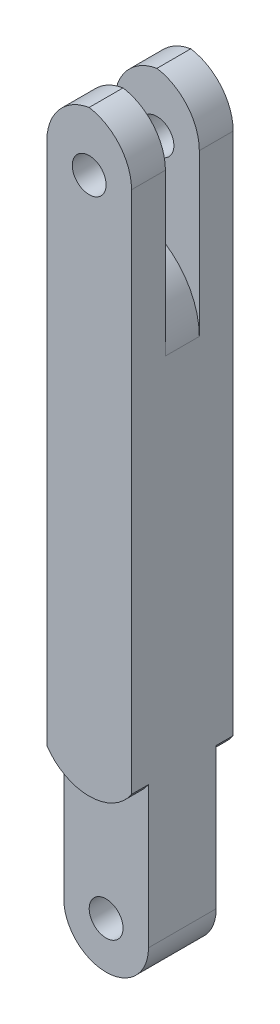
SolidWorks part; units mm, degrees
ref_plane "Alzado" through (0, 0, 0) normal (0, 0, 1) x (1, 0, 0)
ref_plane "Planta" through (0, 0, 0) normal (0, 1, 0) x (1, 0, 0)
ref_plane "Vista lateral" through (0, 0, 0) normal (1, 0, 0) x (0, 0, -1)
sketch "Croquis1" plane through (0, 0, 0) normal (0, 0, 1) x (1, 0, 0)
  line L0 (0, 0) -> (0, 42) construction
  line L1 (-2.5, -0.25) -> (-0.9682, -0.25)
  line L2 (-2.5, -0.25) -> (-2.5, 42)
  line L3 (-2.5, 42) -> (2.5, 42)
  line L4 (2.5, -0.25) -> (2.5, 42)
  line L5 (-4.5017, -1) -> (4.5216, -1) construction
  line L6 (0.9682, -0.25) -> (2.5, -0.25)
  circle A0 centre (0, 0) radius 1 construction
  circle A1 centre (0, 38.5) radius 1
  arc A2 (-0.9682, -0.25) -> (0.9682, -0.25) centre (0, 0) cw
  arc A3 (-2.5, -0.25) -> (2.5, -0.25) centre (0, -0.25) ccw
  circle A4 centre (0, 0) radius 1
  dimension "D1" = 2
  dimension "D3" = 2
  dimension "D7" = 2.5
  dimension "D2" = 0.75
  dimension "D4" = 38.5
  dimension "D5" = 3.5
  dimension "D6" = 5
extrude "Saliente-Extruir1" add sketch "Croquis1" along normal blind 6 contours A4 L1 A3 L6 | L1 A2 L6 L4 L3 L2 A1 region at (0, 20.8126, 0) region at (0, -1.4032, 0)
sketch "Croquis2" plane through (0, 42, 0) normal (0, 1, 0) x (1, 0, 0)
  line L0 (-2.5, -3) -> (2.5, -3) construction
  line L1 (-2.5, -6) -> (-2.5, 0) construction
  line L2 (2.5, -6) -> (2.5, 0) construction
  line L4 (-2.5, -2) -> (2.5, -2)
  line L5 (-2.5, -2) -> (-2.5, -4)
  line L6 (-2.5, -4) -> (2.5, -4)
  line L7 (2.5, -2) -> (2.5, -4)
  dimension "D1" = 2
extrude "Cortar-Extruir1" cut sketch "Croquis2" against normal blind 8
fillet "Redondeo1" radius 4.5 2 edges at (-2.5, 34, 3) (2.5, 34, 3)
fillet "Redondeo2" radius 3 4 edges at (-2.5, 42, 5) (-2.5, 42, 1) (2.5, 42, 1) (2.5, 42, 5)
sketch "Croquis3" plane through (0, 0, 6) normal (0, 0, 1) x (1, 0, 0)
  line L0 (0, 38.5) -> (0, 0) construction
  line L1 (0, 8) -> (0, 25.4165) construction
  line L2 (-3, 8) -> (-3, 25.4165)
  line L3 (3, 8) -> (3, 25.4165)
  line L4 (0, 38.5) -> (0, 25.4165) construction
  line L5 (3, 38.5) -> (3, 25.4165)
  line L6 (-3, 38.5) -> (-3, 25.4165)
  arc A0 (-3, 8) -> (3, 8) centre (0, 8) ccw
  arc A1 (3, 25.4165) -> (-3, 25.4165) centre (0, 25.4165) ccw
  arc A3 (3, 38.5) -> (-3, 38.5) centre (0, 38.5) ccw
  arc A4 (-3, 25.4165) -> (3, 25.4165) centre (0, 25.4165) ccw
  point P6 (0, 16.7082)
  point P11 (0, 31.9582)
  dimension "D1" = 3
  dimension "D2" = 8
extrude "Cortar-Extruir2" [suppressed] cut sketch "Croquis3" against normal through all contours A4 L2 A0 L3 | A1 A4
sketch "Croquis4" plane through (0, 0, 6) normal (0, 0, 1) x (1, 0, 0)
  line L0 (-2.5, -0.25) -> (4.7854, -0.25) construction
  line L1 (-2.5, 8.0917) -> (-2.5, -0.25)
  line L2 (2.5, 8.0917) -> (2.5, -0.25)
  arc A0 (2.5, -0.25) -> (-2.5, -0.25) centre (0, -0.25) cw
  arc A1 (-2.5, -0.25) -> (2.5, -0.25) centre (0, -0.25) ccw construction
  arc A2 (2.5, -0.25) -> (-2.5, -0.25) centre (0, -0.25) ccw construction
  arc A3 (2.5, 8.0917) -> (-2.5, 8.0917) centre (0, 9.75) cw
  point P5 (0, -2.75)
  point P11 (0, -2.75)
  dimension "D2" = 3
  dimension "D1" = 10
extrude "Cortar-Extruir3" cut sketch "Croquis4" against normal blind 1
ref_plane "Plano1" through (0, 0, 3) normal (0, 0, 1) x (1, 0, 0)
mirror "Simetría1" about plane through (0, 0, 3) normal (0, 0, 1) of "Cortar-Extruir3"
